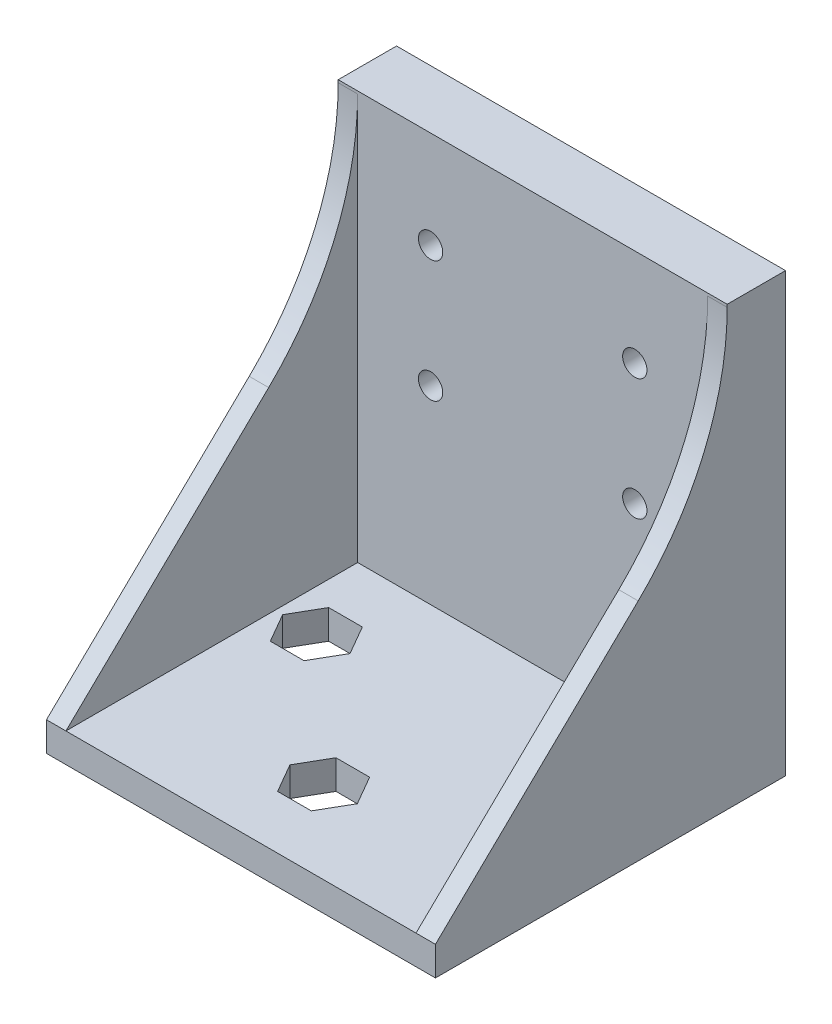
SolidWorks part; units mm, degrees
ref_plane "Front Plane" through (0, 0, 0) normal (0, 0, 1) x (1, 0, 0)
ref_plane "Top Plane" through (0, 0, 0) normal (0, 1, 0) x (1, 0, 0)
ref_plane "Right Plane" through (0, 0, 0) normal (1, 0, 0) x (0, 0, -1)
sketch "Sketch1" plane through (0, 0, 0) normal (0, 1, 0) x (1, 0, 0)
  line L1 (-20, -15) -> (20, -15)
  line L2 (-20, -15) -> (-20, 15)
  line L3 (-20, 15) -> (20, 15)
  line L4 (20, -15) -> (20, 15)
  line L5 (-20, -15) -> (20, 15) construction
  line L6 (-20, 15) -> (20, -15) construction
  point P0 (0, 0)
  dimension "D1" = 30
  dimension "D2" = 40
extrude "Boss-Extrude1" add sketch "Sketch1" along normal blind 3
sketch "Sketch2" plane through (0, 3, 0) normal (0, 1, 0) x (1, 0, 0)
  line L0 (-20, 15) -> (-20, -15) construction
  line L1 (-10.2859, 6.5) -> (-12.0179, 9.5)
  line L2 (-12.0179, 9.5) -> (-15.4821, 9.5)
  line L3 (-15.4821, 9.5) -> (-17.2141, 6.5)
  line L4 (-17.2141, 6.5) -> (-15.4821, 3.5)
  line L5 (-15.4821, 3.5) -> (-12.0179, 3.5)
  line L6 (-12.0179, 3.5) -> (-10.2859, 6.5)
  line L7 (17.2141, 6.5) -> (15.4821, 9.5)
  line L8 (15.4821, 9.5) -> (12.0179, 9.5)
  line L9 (12.0179, 9.5) -> (10.2859, 6.5)
  line L10 (10.2859, 6.5) -> (12.0179, 3.5)
  line L11 (12.0179, 3.5) -> (15.4821, 3.5)
  line L12 (15.4821, 3.5) -> (17.2141, 6.5)
  line L13 (-1.7321, -9.5) -> (1.7321, -9.5)
  line L14 (1.7321, -9.5) -> (3.4641, -6.5)
  line L15 (3.4641, -6.5) -> (1.7321, -3.5)
  line L16 (1.7321, -3.5) -> (-1.7321, -3.5)
  line L17 (-1.7321, -3.5) -> (-3.4641, -6.5)
  line L18 (-3.4641, -6.5) -> (-1.7321, -9.5)
  line L19 (20, 15) -> (-20, 15) construction
  circle A0 centre (-13.75, 6.5) radius 3 construction
  circle A1 centre (13.75, 6.5) radius 3 construction
  circle A2 centre (0, -6.5) radius 3 construction
  point P28 (0, 0)
  dimension "D1" = 6
  dimension "D2" = 27.5
  dimension "D3" = 13.75
  dimension "D4" = 13
  dimension "D5" = 6.25
  dimension "D6" = 8.5
extrude "Cut-Extrude1" cut sketch "Sketch2" against normal up to next
sketch "Sketch3" plane through (0, 0, 0) normal (0, -1, 0) x (1, 0, 0)
  line L0 (-20, -15) -> (-20, 15) construction
  line L1 (20, -15) -> (-20, -15)
  line L2 (20, -15) -> (20, -21)
  line L3 (20, -21) -> (-20, -21)
  line L4 (-20, -15) -> (-20, -21)
  point P5 (0, 0)
  point P6 (0, 0)
  dimension "D1" = 6
extrude "Boss-Extrude2" add sketch "Sketch3" against normal blind 45
sketch "Sketch5" plane through (-20, 0, 0) normal (-1, 0, 0) x (0, 0, 1)
  line L0 (-15, 32) -> (15, 3)
  line L1 (-15, 45) -> (-15, 3) construction
  dimension "D1" = 13
rib "Rib1" sketch "Sketch5" sketch "Sketch5" thickness 2 extrusion direction parallel to sketch draft on no parameters "D1"=2
sketch "Sketch6" plane through (20, 0, 0) normal (1, 0, 0) x (0, 0, -1)
  line L0 (-15, 3) -> (15, 32)
  line L1 (15, 45) -> (15, 3) construction
  dimension "D1" = 13
rib "Rib2" sketch "Sketch6" sketch "Sketch6" thickness 2 extrusion direction parallel to sketch draft on no parameters "D1"=2
fillet "Fillet1" radius 30 2 edges at (19, 32, -15) (-19, 32, -15)
sketch "Sketch7" plane through (0, 0, -21) normal (0, 0, -1) x (-1, 0, 0)
  line L1 (-15, 5) -> (15, 5)
  line L2 (-15, 5) -> (-15, 40)
  line L3 (-15, 40) -> (15, 40)
  line L4 (15, 5) -> (15, 40)
  line L5 (-20, 45) -> (-20, 0) construction
  line L6 (20, 45) -> (-20, 45) construction
  circle A0 centre (-10.5, 35) radius 2.25
  circle A1 centre (10.5, 35) radius 2.25
  circle A2 centre (10.5, 22.5) radius 2.25
  circle A3 centre (-10.5, 22.5) radius 2.25
  point P16 (0, 0)
  point P17 (0, 0)
  point P18 (0, 0)
  point P19 (0, 0)
  dimension "D5" = 4.5
  dimension "D1" = 30
  dimension "D2" = 35
  dimension "D3" = 5
  dimension "D4" = 5
  dimension "D6" = 21
  dimension "D7" = 4.5
  dimension "D8" = 12.5
  dimension "D9" = 5
extrude "Cut-Extrude2" cut sketch "Sketch7" against normal blind 2.5
hole_wizard "Ø2.5mm Dowel Hole1" positions "Sketch8" profile "Sketch9" hole size "Ø2.5" standard "ANSI Metric" end condition up to next
sketch "Sketch8" plane through (0, 0, -21) normal (0, 0, -1) x (-1, 0, 0)
  circle A0 centre (-10.5, 35) radius 2.25 construction
  circle A1 centre (10.5, 35) radius 2.25 construction
  circle A2 centre (10.5, 22.5) radius 2.25 construction
  circle A3 centre (-10.5, 22.5) radius 2.25 construction
  point P0 (10.5, 35)
  point P2 (-10.5, 35)
  point P4 (-10.5, 22.5)
  point P6 (10.5, 22.5)
  point P11 (0, 0)
  point P12 (0, 0)
  point P15 (0, 0)
  point P18 (0, 0)
sketch "Sketch9" plane through (-10.5, 35, -21) normal (1, 0, 0) x (0, 1, 0)
  line L0 (0, 0) -> (0, 6)
  line L1 (0, 6) -> (1.25, 6)
  line L2 (1.25, 6) -> (1.25, 0)
  line L5 (1.25, 0) -> (0, 0)
  line L11 (0, -6.35) -> (0, 107.95) construction
  dimension "Thru Hole Dia." = 2.5
  dimension "Thru Hole Depth" = 6
